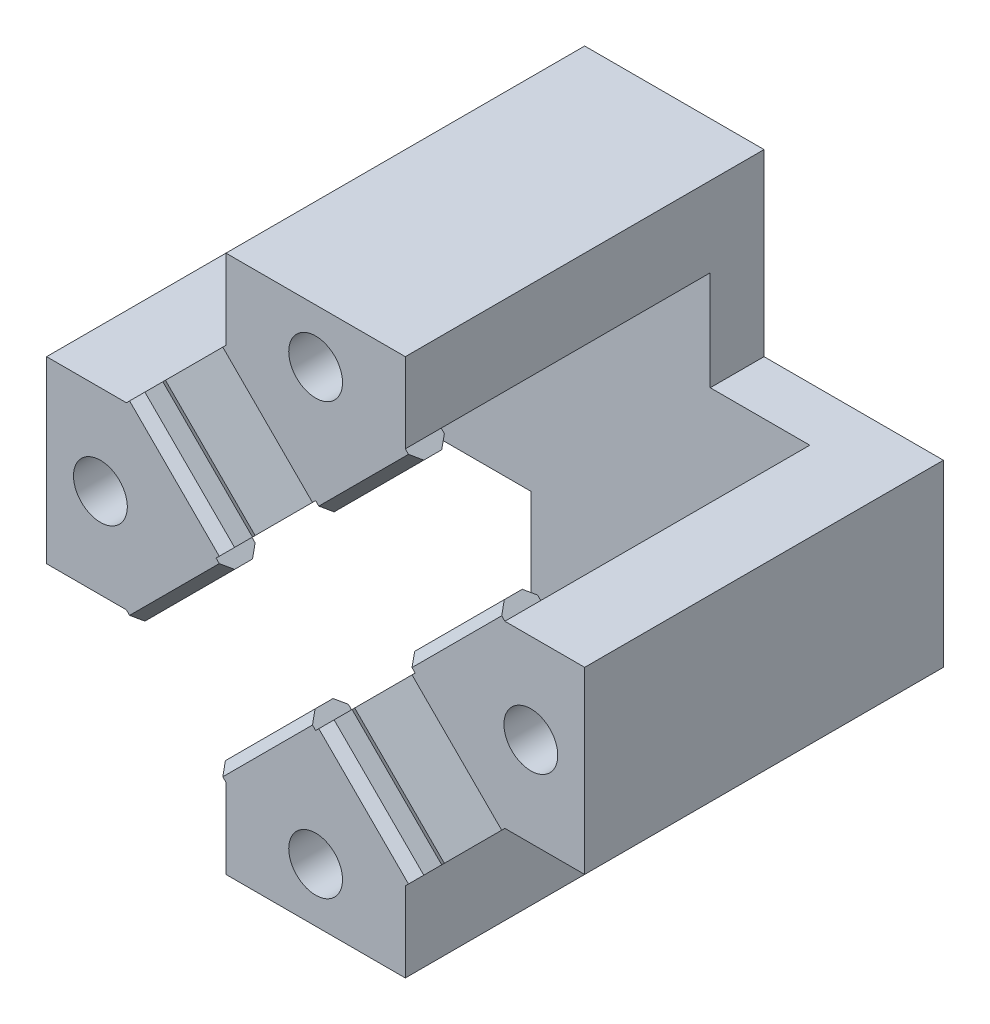
SolidWorks part; units mm, degrees
ref_plane "Plan de face" through (0, 0, 0) normal (0, 0, 1) x (1, 0, 0)
ref_plane "Plan de dessus" through (0, 0, 0) normal (0, 1, 0) x (1, 0, 0)
ref_plane "Plan de droite" through (0, 0, 0) normal (1, 0, 0) x (0, 0, -1)
sketch "Esquisse1" plane through (0, 0, 0) normal (0, 0, 1) x (1, 0, 0)
  line L1 (-5.269, 9.0535) -> (4.731, 9.0535)
  line L2 (-5.269, 9.0535) -> (-5.269, -20.9465)
  line L3 (-5.269, -20.9465) -> (4.731, -20.9465)
  line L4 (4.731, 9.0535) -> (4.731, -20.9465)
  line L5 (-15.269, -0.9465) -> (14.731, -0.9465)
  line L6 (-15.269, -0.9465) -> (-15.269, -10.9465)
  line L7 (-15.269, -10.9465) -> (14.731, -10.9465)
  line L8 (14.731, -0.9465) -> (14.731, -10.9465)
  point P8 (-15.269, -5.9465)
  point P9 (-5.269, -5.9465)
  dimension "D1" = 10
  dimension "D2" = 30
  dimension "D3" = 10
  dimension "D4" = 30
  dimension "D5" = 10
  dimension "D6" = 0
extrude "Boss.-Extru.1" add sketch "Esquisse1" along normal blind 3 contours L2 L7 L4 L5 | L6 L7 L2 L5 | L2 L5 L4 L1 | L8 L5 L4 L7 | L7 L2 L3 L4 region at (-0.269, 4.0535, 0) region at (-0.269, -5.9465, 0) region at (-10.269, -5.9465, 0) region at (9.731, -5.9465, 0) region at (-0.269, -15.9465, 0)
sketch "Esquisse2" plane through (0, 0, 3) normal (0, 0, 1) x (1, 0, 0)
  line L0 (-5.269, 4.6035) -> (-0.269, -0.3965)
  line L1 (-5.269, 9.0535) -> (4.731, 9.0535)
  line L2 (-5.269, 9.0535) -> (-5.269, 4.6035)
  line L3 (-0.269, -0.3965) -> (4.731, 4.6035)
  line L4 (4.731, 9.0535) -> (4.731, 4.6035)
  line L5 (-15.269, -5.9465) -> (14.731, -5.9465) construction
  line L8 (-0.269, 9.0535) -> (-0.269, -20.9465) construction
  line L10 (4.731, -20.9465) -> (4.731, -16.4965)
  line L11 (-0.269, -11.4965) -> (4.731, -16.4965)
  line L12 (-5.269, -20.9465) -> (-5.269, -16.4965)
  line L13 (-5.269, -20.9465) -> (4.731, -20.9465)
  line L14 (-5.269, -16.4965) -> (-0.269, -11.4965)
  line L15 (-10.819, -0.9465) -> (-5.819, -5.9465)
  line L16 (-15.269, -0.9465) -> (-10.819, -0.9465)
  line L17 (-15.269, -0.9465) -> (-15.269, -10.9465)
  line L18 (-15.269, -10.9465) -> (-10.819, -10.9465)
  line L19 (-5.819, -5.9465) -> (-10.819, -10.9465)
  line L20 (5.281, -5.9465) -> (10.281, -10.9465)
  line L21 (14.731, -10.9465) -> (10.281, -10.9465)
  line L22 (14.731, -0.9465) -> (14.731, -10.9465)
  line L23 (14.731, -0.9465) -> (10.281, -0.9465)
  line L24 (10.281, -0.9465) -> (5.281, -5.9465)
  dimension "D1" = 135
  dimension "D2" = 135
  dimension "D3" = 0
  dimension "D4" = 9.45
  dimension "D5" = 0
  dimension "D6" = 135
  dimension "D7" = 135
  dimension "D8" = 9.45
extrude "Boss.-Extru.2" add sketch "Esquisse2" along normal blind 17
sketch "Esquisse3" plane through (0, 0, 0) normal (0, 0, -1) x (-1, 0, 0)
  line L1 (5.269, 9.0535) -> (-4.731, 9.0535) construction
  line L2 (-14.731, -0.9465) -> (-14.731, -10.9465) construction
  line L3 (15.269, -0.9465) -> (15.269, -10.9465) construction
  line L4 (5.269, -20.9465) -> (-4.731, -20.9465) construction
  circle A0 centre (0.269, 6.0535) radius 1.5
  circle A1 centre (-11.731, -5.9465) radius 1.5
  circle A2 centre (12.269, -5.9465) radius 1.5
  circle A3 centre (0.269, -17.9465) radius 1.5
  point P16 (0.269, -20.9465)
  dimension "D2" = 3
  dimension "D3" = 3
  dimension "D4" = 3
  dimension "D5" = 3
  dimension "D6" = 3
  dimension "D7" = 3
  dimension "D8" = 3
  dimension "D1" = 3
extrude "Enlèv. mat.-Extru.1" cut sketch "Esquisse3" against normal through all both and the other way through all
sketch "Esquisse4" plane through (-0.3328, -0.3328, 0) normal (-0.7071, -0.7071, 0) x (0, 0, 1)
  line L0 (20, -0.0902) -> (3, -0.0902) construction
  line L1 (20, 6.9809) -> (18, 6.9809)
  line L2 (20, 6.9809) -> (20, -0.0902)
  line L3 (20, -0.0902) -> (18, -0.0902)
  line L4 (18, 6.9809) -> (18, -0.0902)
  line L5 (20, -7.9391) -> (3, -7.9391) construction
  line L6 (20, -15.0101) -> (18, -15.0101)
  line L7 (20, -15.0101) -> (20, -7.9391)
  line L8 (20, -7.9391) -> (18, -7.9391)
  line L9 (18, -15.0101) -> (18, -7.9391)
  dimension "D1" = 2
  dimension "D2" = 2
extrude "Boss.-Extru.3" add sketch "Esquisse4" along normal blind 0.75
sketch "Esquisse5" plane through (-5.8828, -5.8828, 0) normal (0.7071, 0.7071, 0) x (0, 0, -1)
  line L0 (-20, 6.9809) -> (-3, 6.9809) construction
  line L1 (-20, -0.0902) -> (-18, -0.0902)
  line L2 (-20, -0.0902) -> (-20, 6.9809)
  line L3 (-20, 6.9809) -> (-18, 6.9809)
  line L4 (-18, -0.0902) -> (-18, 6.9809)
  line L5 (-20, -15.0101) -> (-3, -15.0101) construction
  line L6 (-20, -7.9391) -> (-18, -7.9391)
  line L7 (-20, -7.9391) -> (-20, -15.0101)
  line L8 (-20, -15.0101) -> (-18, -15.0101)
  line L9 (-18, -7.9391) -> (-18, -15.0101)
  dimension "D1" = 2
  dimension "D2" = 2
extrude "Boss.-Extru.4" add sketch "Esquisse5" along normal blind 0.75
sketch "Esquisse6" plane through (5.6138, -5.6138, 0) normal (-0.7071, 0.7071, 0) x (0, 0, 1)
  line L0 (18, -8.3195) -> (3, -8.3195) construction
  line L1 (20, -15.3906) -> (18, -15.3906)
  line L2 (20, -15.3906) -> (20, -8.3195)
  line L3 (20, -8.3195) -> (18, -8.3195)
  line L4 (18, -15.3906) -> (18, -8.3195)
  line L5 (18, -0.4706) -> (3, -0.4706) construction
  line L6 (20, 6.6005) -> (18, 6.6005)
  line L7 (20, 6.6005) -> (20, -0.4706)
  line L8 (20, -0.4706) -> (18, -0.4706)
  line L9 (18, 6.6005) -> (18, -0.4706)
  dimension "D1" = 2
  dimension "D2" = 2
extrude "Boss.-Extru.5" add sketch "Esquisse6" along normal blind 0.75
sketch "Esquisse7" plane through (0.0638, -0.0638, 0) normal (0.7071, -0.7071, 0) x (0, 0, -1)
  line L0 (-18, -8.3195) -> (-3, -8.3195) construction
  line L1 (-20, -15.3906) -> (-18, -15.3906)
  line L2 (-20, -15.3906) -> (-20, -8.3195)
  line L3 (-20, -8.3195) -> (-18, -8.3195)
  line L4 (-18, -15.3906) -> (-18, -8.3195)
  line L5 (-18, -0.4706) -> (-3, -0.4706) construction
  line L6 (-20, 6.6005) -> (-18, 6.6005)
  line L7 (-20, 6.6005) -> (-20, -0.4706)
  line L8 (-20, -0.4706) -> (-18, -0.4706)
  line L9 (-18, 6.6005) -> (-18, -0.4706)
  dimension "D1" = 2
  dimension "D2" = 2
extrude "Boss.-Extru.6" add sketch "Esquisse7" along normal blind 0.75
chamfer "Chanfrein1" distance 0.5 angle 45 16 edges at (-3.2993, -13.4662, 18) (-3.2993, -13.4662, 20) (7.2507, -2.9162, 20) (7.2507, -2.9162, 18) (-7.7887, -8.9769, 18) (-7.7887, -8.9769, 20) (-7.7887, -2.9162, 18) (-7.7887, -2.9162, 20) (-3.2993, 1.5731, 18) (-3.2993, 1.5731, 20) (2.7613, 1.5731, 20) (2.7613, 1.5731, 18) (7.2507, -8.9769, 18) (7.2507, -8.9769, 20) (2.7613, -13.4662, 20) (2.7613, -13.4662, 18)
